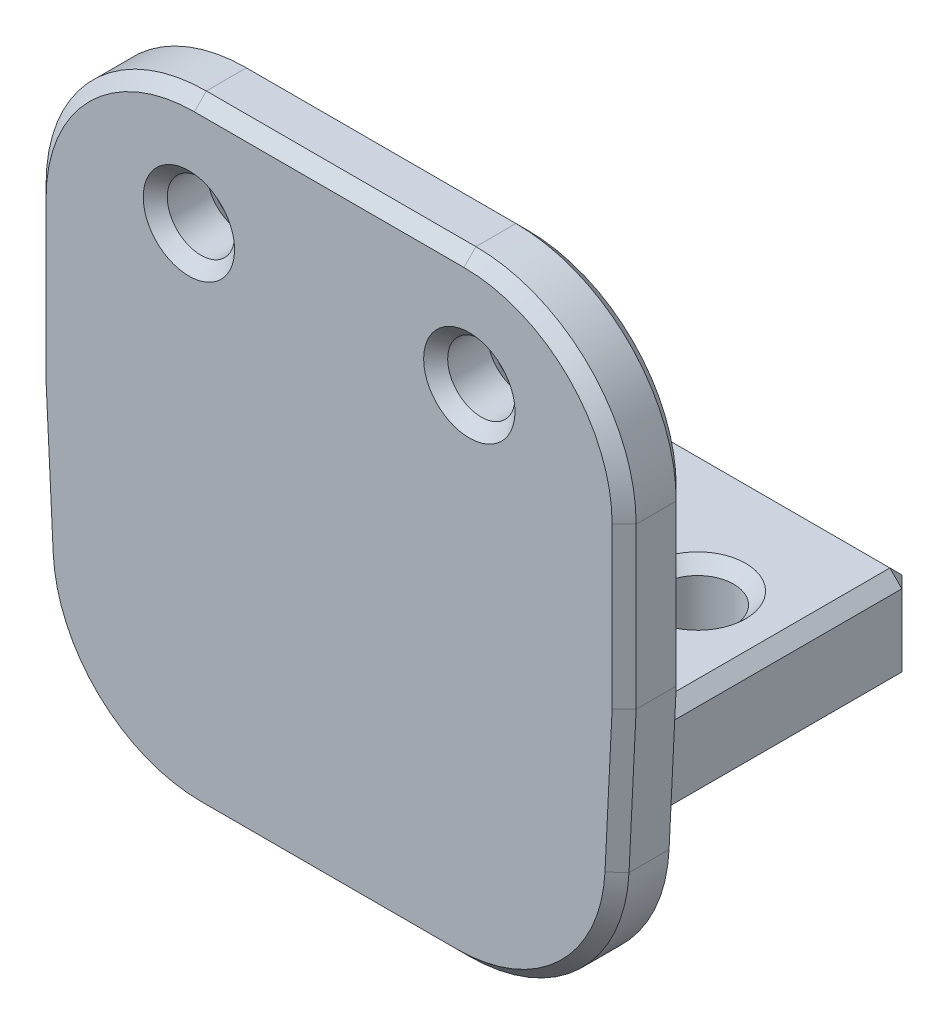
SolidWorks part; units mm, degrees
ref_plane "Front Plane" through (0, 0, 0) normal (0, 0, 1) x (1, 0, 0)
ref_plane "Top Plane" through (0, 0, 0) normal (0, 1, 0) x (1, 0, 0)
ref_plane "Right Plane" through (0, 0, 0) normal (1, 0, 0) x (0, 0, -1)
sketch "Sketch1" plane through (0, 0, 0) normal (0, 1, 0) x (1, 0, 0)
  line L1 (0, 0) -> (25, 0)
  line L2 (0, 0) -> (0, 25)
  line L3 (0, 25) -> (25, 25)
  line L4 (25, 0) -> (25, 25)
  dimension "D1" = 25
  dimension "D2" = 25
extrude "Boss-Extrude1" add sketch "Sketch1" along normal blind 6
sketch "Sketch5" plane through (0, 0, 0) normal (0, 0, 1) x (1, 0, 0)
  line L7 (-5.9133, 12.95) -> (30.915, 12.95)
  line L10 (30, -5.62) -> (30.915, 12.95)
  line L11 (0, 6) -> (25, 6) construction
  line L12 (12.5008, 12.95) -> (12.5, -5.62) construction
  line L13 (-5.9133, 12.95) -> (-5, -5.62)
  line L14 (-5, -5.62) -> (30, -5.62)
  point P10 (12.5, 6)
  dimension "D1" = 35
  dimension "D2" = 36.8283
  dimension "D3" = 6.95
  dimension "D6" = 18.415
extrude "Boss-Extrude3" add sketch "Sketch5" against normal blind 4
fillet "Fillet1" [suppressed] radius 2
sketch "Sketch2" plane through (0, 0, 0) normal (0, -1, 0) x (1, 0, 0)
  line L0 (12.5, 0) -> (12.5, -25) construction
  line L1 (0, 0) -> (25, 0) construction
  line L2 (25, -25) -> (0, -25) construction
  line L3 (-5, -4) -> (30, -4) construction
  circle A0 centre (5.5, -16) radius 2.25
  circle A1 centre (19.5, -16) radius 2.25
  dimension "D1" = 7
  dimension "D3" = 4.5
  dimension "D4" = 12
extrude "Cut-Extrude1" cut sketch "Sketch2" against normal blind 6
sketch "Sketch9" plane through (0, 0, -25) normal (0, 0, -1) x (-1, 0, 0)
  line L1 (-25, 6) -> (0, 6)
  line L2 (-25, 6) -> (-25, 0)
  line L3 (-25, 0) -> (0, 0)
  line L4 (0, 6) -> (0, 0)
extrude "Cut-Extrude2" cut sketch "Sketch9" against normal blind 1
sketch "Sketch10" plane through (0, 6, 0) normal (0, 1, 0) x (1, 0, 0)
  line L0 (0, 4) -> (0, 10)
  line L1 (0, 24) -> (0, 4) construction
  line L2 (0, 10) -> (25, 10)
  line L3 (25, 4) -> (25, 24) construction
  line L4 (0, 24) -> (0, 10)
  dimension "D1" = 6
sketch "Sketch11" plane through (0, 12.95, 0) normal (0, 1, 0) x (1, 0, 0)
  line L4 (-5.9133, 0) -> (30.915, 0)
  line L5 (30.915, 0) -> (30.915, 4)
  line L6 (30.915, 4) -> (-5.9133, 4)
  line L7 (-5.9133, 4) -> (-5.9133, 0)
  line L8 (-5.9133, 0) -> (30.915, 0)
  line L9 (30.915, 0) -> (30.915, 4)
  line L10 (30.915, 4) -> (-5.9133, 4)
  line L11 (-5.9133, 4) -> (-5.9133, 0)
  dimension "D1" = 0
extrude "Boss-Extrude4" add sketch "Sketch11" along normal blind 20
sketch "Sketch13" plane through (0, 0, -4) normal (0, 0, -1) x (-1, 0, 0)
  line L0 (-12.5, 6) -> (-12.5, 26) construction
  line L1 (0, 6) -> (-25, 6) construction
  line L2 (-21.25, 26) -> (-3.75, 26) construction
  circle A0 centre (-21.25, 26) radius 2.1
  circle A1 centre (-3.75, 26) radius 2.1
  point P7 (-12.5, 26)
  dimension "D3" = 4.2
  dimension "D4" = 4.2
  dimension "D1" = 20
  dimension "D2" = 17.5
extrude "Cut-Extrude3" cut sketch "Sketch13" against normal through all
fillet "Fillet2" radius 10 4 edges at (30, -5.62, -2) (-5, -5.62, -2) (-5.9133, 32.95, -2) (30.915, 32.95, -2)
chamfer "Chamfer1" distance 0.75 angle 45 24 edges at (-2.3749, -2.8627, 0) (-5.6905, 8.4194, 0) (-5.9133, 17.95, 0) (-2.9844, 30.0211, 0) (12.5008, 32.95, 0) (27.9861, 30.0211, 0) (30.915, 17.95, 0) (30.6917, 8.4189, 0) (27.3755, -2.863, 0) (12.5004, -5.62, 0) (1.65, 26, 0) (19.15, 26, 0) (30.6917, 8.4189, -4) (27.3755, -2.863, -4) (12.5004, -5.62, -4) (-5.6905, 8.4194, -4) (-2.3749, -2.8627, -4) (30.915, 17.95, -4) (27.9861, 30.0211, -4) (-5.9133, 17.95, -4) (12.5008, 32.95, -4) (-2.9844, 30.0211, -4) (19.15, 26, -4) (1.65, 26, -4)
chamfer "Chamfer2" distance 0.75 angle 45 4 edges at (19.5, 6, -13.75) (19.5, 0, -13.75) (5.5, 0, -18.25) (5.5, 6, -18.25)
chamfer "Chamfer3" distance 0.75 angle 45 8 edges at (12.5, 6, -24) (0, 6, -14) (0, 3, -24) (25, 6, -14) (25, 3, -24) (25, 0, -14) (12.5, 0, -24) (0, 0, -14)
